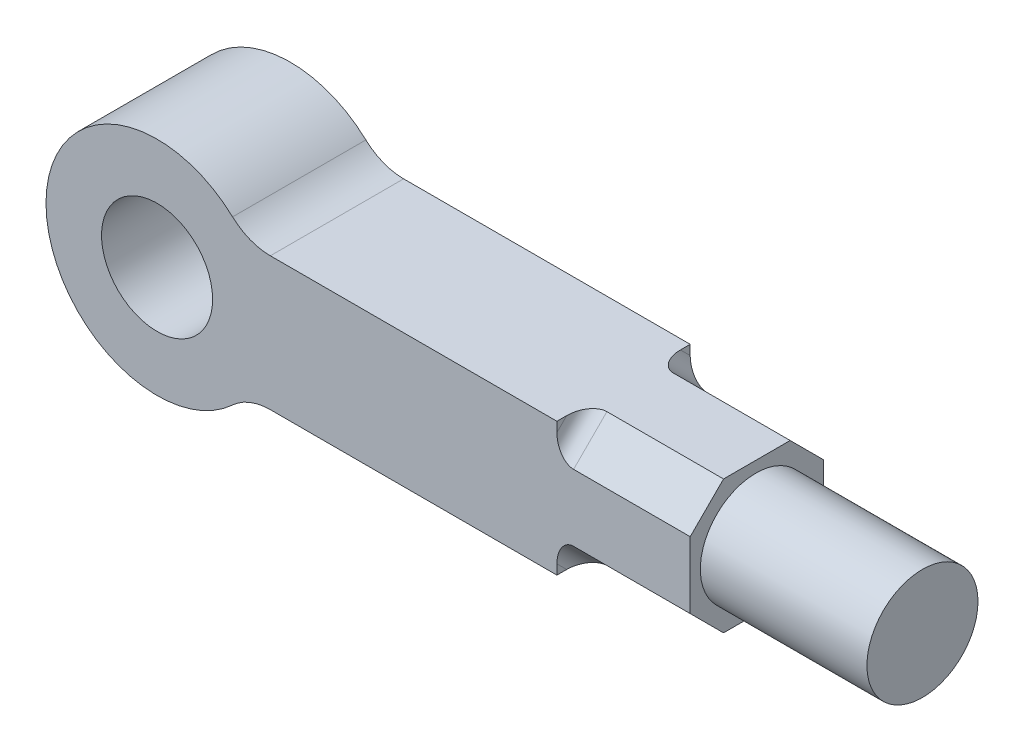
SolidWorks part; units mm, degrees
note: The reader was unsure of these and kept them because the rebuilt part matched: shared geometry of "Sketch2<3>".
ref_plane "Front Plane" through (0, 0, 0) normal (0, 0, 1) x (1, 0, 0)
ref_plane "Top Plane" through (0, 0, 0) normal (0, 1, 0) x (1, 0, 0)
ref_plane "Right Plane" through (0, 0, 0) normal (1, 0, 0) x (0, 0, -1)
sketch "Sketch1" plane through (0, 0, 0) normal (0, 0, 1) x (1, 0, 0)
  line L0 (0, 0) -> (10, 0) construction
  line L1 (96, 0) -> (166.9917, 0) construction
  line L2 (20.3961, 12) -> (96, 12)
  line L4 (20.3961, -12) -> (96, -12)
  line L5 (96, 12) -> (96, -12)
  arc A0 (13.5974, 14.6667) -> (13.5974, -14.6667) centre (0, 0) ccw
  circle A1 centre (0, 0) radius 10
  arc A2 (13.5974, -14.6667) -> (20.3961, -12) centre (20.3961, -22) cw
  arc A3 (20.3961, 12) -> (13.5974, 14.6667) centre (20.3961, 22) cw
  point P14 (16, 12)
  dimension "D1" = 40
  dimension "D2" = 20
  dimension "D5" = 10
  dimension "D3" = 80
  dimension "D4" = 24
extrude "Boss-Extrude1" add sketch "Sketch1" along normal blind 24
sketch "Sketch2" plane through (96, 0, 0) normal (1, 0, 0) x (0, 0, -1)
  line L0 (-24, 12) -> (-24, 6)
  line L1 (0, 12) -> (-6, 12)
  line L2 (0, 12) -> (0, 6)
  line L3 (-24, -12) -> (-24, 12) construction
  line L4 (0, -12) -> (0, 12) construction
  line L5 (-24, 12) -> (-18, 12)
  line L6 (-24, 12) -> (0, 12) construction
  line L7 (-24, 6) -> (-18, 12)
  line L8 (-6, 12) -> (0, 6)
  line L9 (-24, -12) -> (-24, -6)
  line L10 (-24, -12) -> (-18, -12)
  line L11 (-24, -12) -> (0, -12) construction
  line L12 (-18, -12) -> (-24, -6)
  line L13 (0, -12) -> (-6, -12)
  line L14 (0, -12) -> (0, -6)
  line L15 (-5.6208, -12) -> (0, -6)
  circle A1 centre (-12.1791, 0) radius 10
  dimension "D1" = 20
  dimension "D2" = 6
  dimension "D3" = 6
  dimension "D4" = 6
extrude "Cut-Extrude1" cut sketch "Sketch2" against normal blind 24
extrude "Boss-Extrude4" add sketch "Sketch2<3>" along normal blind 30 contours A1
sketch "Sketch2<3>" plane through (96, 0, 0) normal (1, 0, 0) x (0, 0, -1) same geometry as "Sketch2"
fillet "Fillet7" radius 3 4 edges at (72, -9, 2.8104) (72, -9, 21) (72, 9, 21) (72, 9, 3)
